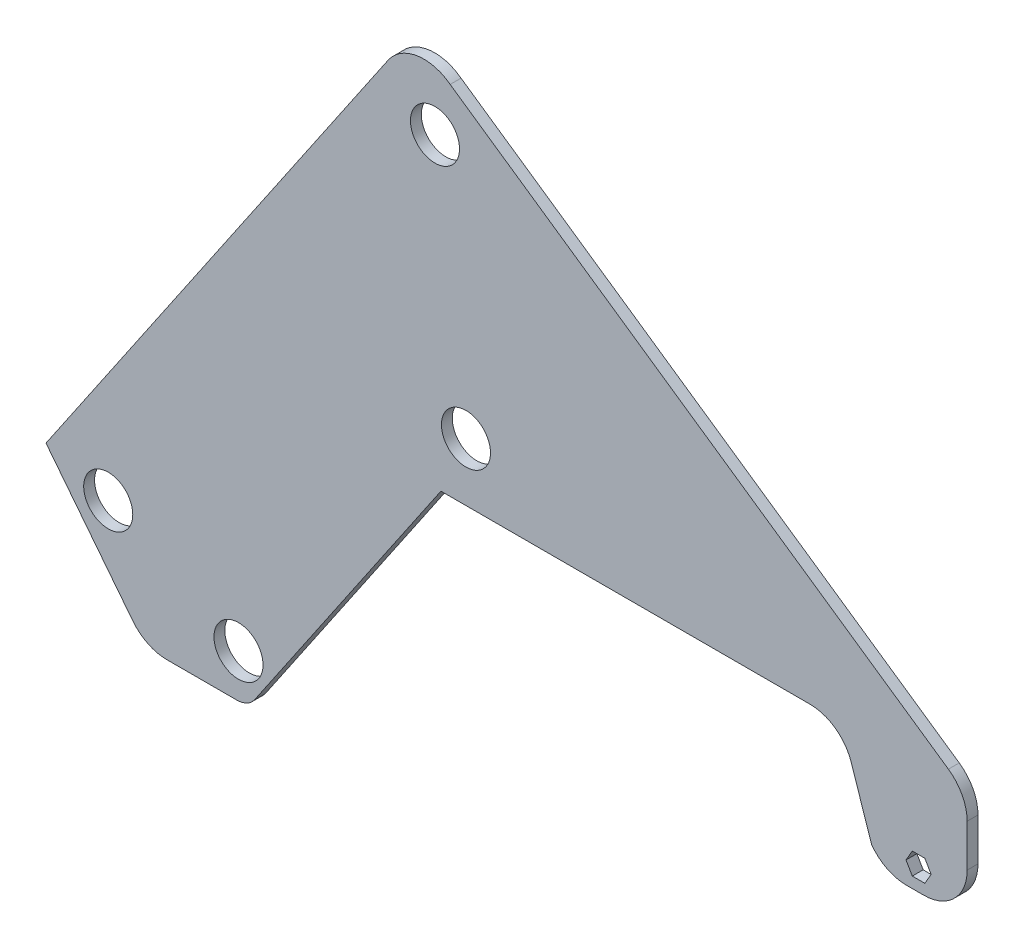
SolidWorks part; units mm, degrees
other "Markup1"
sketch "Sketch1" plane through (-441.7893, 331.8239, 6.35) normal (-0.0431, 0.0102, 0.999) x (0.9985, 0.0354, 0.0427)
sketch "Sketch2" plane through (-413.6701, 343.933, 6.35) normal (-0.0431, 0.0102, 0.999) x (0.9985, 0.0354, 0.0427)
ref_plane "Front Plane" through (0, 0, 0) normal (0, 0, 1) x (1, 0, 0)
ref_plane "Top Plane" through (0, 0, 0) normal (0, 1, 0) x (1, 0, 0)
ref_plane "Right Plane" through (0, 0, 0) normal (1, 0, 0) x (0, 0, -1)
sketch "Model" plane through (0, 0, 0) normal (0, 0, 1) x (1, 0, 0)
  line L1 (-205.3388, 104.6502) -> (-2.1388, 104.6502)
  line L3 (-314.2383, -55.3595) -> (-205.3388, 104.6502)
  line L4 (-236.3032, 307.4477) -> (-436.3774, 13.472)
  line L5 (-436.3774, 13.472) -> (-385.5815, -51.2028)
  line L13 (81.3935, 53.8502) -> (77.7274, 60.2002)
  line L14 (77.7274, 60.2002) -> (70.395, 60.2002)
  line L15 (70.395, 60.2002) -> (66.7288, 53.8502)
  line L16 (66.7288, 53.8502) -> (70.395, 47.5002)
  line L17 (70.395, 47.5002) -> (77.7274, 47.5002)
  line L18 (77.7274, 47.5002) -> (81.3935, 53.8502)
  line L19 (-365.606, -60.914) -> (-324.7375, -60.914)
  line L20 (-871.0211, -88.854) -> (370.1019, -88.854) construction
  line L22 (102.4721, 66.5502) -> (102.4721, 83.8724)
  line L27 (67.0531, 41.1502) -> (77.0721, 41.1502)
  line L28 (-399.9752, 2.586) -> (-323.7752, -35.514) construction
  line L29 (-323.7752, -35.514) -> (-190.7071, 138.5169) construction
  line L30 (-190.7071, 138.5169) -> (-208.8329, 283.4378) construction
  line L31 (-208.8329, 283.4378) -> (-399.9752, 2.586) construction
  line L32 (46.5921, 51.5001) -> (34.6564, 87.2866)
  line L33 (10.5612, 104.6502) -> (-11.3966, 104.6502)
  line L34 (102.4721, 83.8724) -> (102.4721, 91.319)
  line L35 (91.5006, 112.2231) -> (-199.9496, 313.3896)
  circle A9 centre (-323.7752, -35.514) radius 14.351
  circle A10 centre (-399.9752, 2.586) radius 14.351
  circle A12 centre (-190.7071, 138.5169) radius 14.351
  circle A22 centre (-208.8329, 283.4378) radius 14.351
  circle A24 centre (74.0612, 53.8502) radius 6.35 construction
  arc A31 (-324.7375, -60.914) -> (-314.2383, -55.3595) centre (-324.7375, -48.214) ccw
  arc A40 (46.5921, 51.5001) -> (67.0531, 41.1502) centre (67.0531, 66.5502) ccw
  arc A43 (77.0721, 41.1502) -> (102.4721, 66.5502) centre (77.0721, 66.5502) ccw
  arc A44 (-236.3032, 307.4477) -> (-199.9496, 313.3896) centre (-215.305, 293.1567) cw
  arc A45 (-365.606, -60.914) -> (-385.5815, -51.2028) centre (-365.606, -35.514) cw
  arc A46 (34.6564, 87.2866) -> (10.5612, 104.6502) centre (10.5612, 79.2502) ccw
  arc A47 (102.4721, 91.319) -> (91.5006, 112.2231) centre (77.0721, 91.319) ccw
  point P31 (-221.2548, 329.5588)
  point P34 (100.2935, -12.8222)
  point P36 (0, 0)
  point P43 (-377.9543, -60.914)
  point P46 (0, 0)
  point P59 (174.831, 53.8502)
  dimension "D3" = 38.1
  dimension "D4" = 104.6502
  dimension "D5" = 76.2
  dimension "D6" = 25.4
  dimension "D7" = 12.7
  dimension "D8" = 28.702
  dimension "D11" = 139.7
  dimension "D12" = 27.94
  dimension "D21" = 124.238
  dimension "D13" = 12.7
  dimension "D16" = 355.6
  dimension "D23" = 25.4
  dimension "D24" = 25.4
  dimension "D26" = 25.4
  dimension "D14" = 406.4
  dimension "D20" = 215.9
  dimension "D29" = 25.4
  dimension "D31" = 25.4
  dimension "D9" = 19.05
  dimension "D10" = 146.05
  dimension "D15" = 33.8667
  dimension "D17" = 339.725
  dimension "D18" = 219.075
  dimension "D19" = 50.8
  dimension "D22" = 25.4
  dimension "D27" = 53.2168
  dimension "D28" = 12.7
  dimension "D30" = 55.88
extrude "Boss-Extrude1" add sketch "Model" along normal blind 6.35 contours L5 L3 L1 L4 A22 A9 A10 A12 region at (-265.237, 28.3535, 0)
